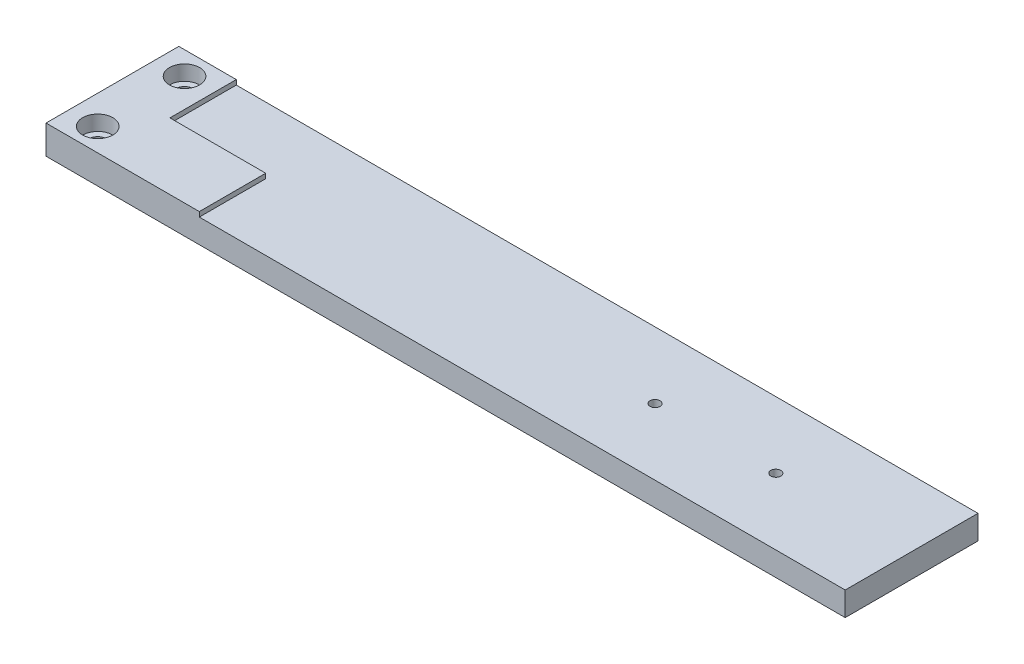
SolidWorks part; units mm, degrees
material "6061 Alloy"
ref_plane "Front" through (0, 0, 0) normal (0, 0, 1) x (1, 0, 0)
ref_plane "Top" through (0, 0, 0) normal (0, 1, 0) x (1, 0, 0)
ref_plane "Right" through (0, 0, 0) normal (1, 0, 0) x (0, 0, -1)
sketch "Sketch1" plane through (0, 0, 0) normal (0, 1, 0) x (1, 0, 0)
  line L1 (0, 0) -> (220.35, 0)
  line L2 (0, 0) -> (0, 44)
  line L3 (0, 44) -> (220.35, 44)
  line L4 (220.35, 0) -> (220.35, 44)
  dimension "D1" = 44
  dimension "D2" = 220.35
extrude "Boss-Extrude1" add sketch "Sketch1" along normal blind 7.9375
sketch "Sketch2" plane through (0, 7.9375, 0) normal (0, 1, 0) x (1, 0, 0)
  line L1 (0, 0) -> (6.35, 0)
  line L2 (0, 0) -> (0, 22)
  line L3 (0, 22) -> (6.35, 22)
  line L4 (6.35, 0) -> (6.35, 22)
  line L5 (0, 0) -> (220.35, 0) construction
  dimension "D1" = 6.35
  dimension "D2" = 22
extrude "Boss-Extrude2" add sketch "Sketch2" along normal blind 1.5875
hole_wizard "M4x0.7 Tapped Hole2" positions "Sketch5" profile "Sketch6" tap size "M4x0.7" standard "ANSI Metric" end condition through all
sketch "Sketch5" plane through (0, 7.9375, 0) normal (0, 1, 0) x (1, 0, 0)
  line L0 (220.35, 22) -> (135.35, 22) construction
  line L1 (220.35, 0) -> (220.35, 44) construction
  point P0 (135.35, 22)
  point P2 (175.35, 22)
  dimension "D1" = 85
  dimension "D2" = 40
sketch "Sketch6" plane through (135.35, 7.9375, -22) normal (1, 0, 0) x (0, 0, 1)
  line L0 (0, 0) -> (0, 7.9375)
  line L1 (0, 7.9375) -> (1.65, 7.9375)
  line L2 (1.65, 7.9375) -> (1.65, 0)
  line L5 (1.65, 0) -> (0, 0)
  line L11 (0, -6.35) -> (0, 107.95) construction
  dimension "Thru Tap Drill Dia." = 3.3
  dimension "Thru Tap Drill Depth" = 7.9375
cosmetic thread "Hole Thread1" parameters "D2"=4
cosmetic thread "Hole Thread2" parameters "D2"=4
sketch "Sketch7" plane through (0, 0, 0) normal (0, 1, 0) x (1, 0, 0)
  line L0 (0, -50) -> (0, 50) construction
  line L1 (0, 44) -> (-44.45, 44)
  line L2 (0, 44) -> (0, 0)
  line L3 (0, 0) -> (-44.45, 0)
  line L4 (-44.45, 44) -> (-44.45, 0)
  line L5 (220.35, 44) -> (0, 44) construction
  line L6 (-50, 0) -> (50, 0) construction
  dimension "D1" = 44.45
extrude "Boss-Extrude3" add sketch "Sketch7" along normal blind 9.525
hole_wizard "CBORE for M5 SHCS1" positions "Sketch12" profile "Sketch13" counterbore size "M5" standard "ANSI Metric" end condition through all
sketch "Sketch12" plane through (0, 9.525, 0) normal (0, 1, 0) x (1, 0, 0)
  line L1 (0, 44) -> (-44.45, 44) construction
  line L2 (-50, 0) -> (50, 0) construction
  line L3 (-44.45, 44) -> (-44.45, 0) construction
  point P0 (-34.925, 36.38)
  point P2 (-34.925, 7.62)
  dimension "D1" = 7.62
  dimension "D2" = 7.62
  dimension "D3" = 9.525
  dimension "D4" = 9.525
sketch "Sketch13" plane through (-34.925, 9.525, -36.38) normal (1, 0, 0) x (0, 0, 1)
  line L0 (0, 0) -> (0, 9.525)
  line L1 (0, 9.525) -> (2.9, 9.525)
  line L3 (2.9, 9.525) -> (2.9, 5)
  line L4 (2.9, 5) -> (5, 5)
  line L5 (5, 5) -> (5, 0)
  line L7 (5, 0) -> (0, 0)
  line L11 (0, -6.35) -> (0, 107.95) construction
  dimension "Thru Hole Dia." = 5.8
  dimension "Thru Hole Depth" = 9.525
  dimension "C'Bore Dia." = 10
  dimension "C'Bore Depth" = 5
sketch "Sketch14" plane through (0, 9.525, 0) normal (0, 1, 0) x (1, 0, 0)
  line L0 (0, -50) -> (0, 50) construction
  line L1 (0, 44) -> (-25.4, 44)
  line L2 (0, 44) -> (0, 22)
  line L3 (0, 22) -> (-25.4, 22)
  line L4 (-25.4, 44) -> (-25.4, 22)
  line L5 (0, 44) -> (-44.45, 44) construction
  line L9 (6.35, 22) -> (0, 22) construction
  dimension "D1" = 25.4
extrude "Cut-Extrude1" cut sketch "Sketch14" along direction (0, -1, 0) on the side against the normal up to surface (1.5875 mm away) up to face at (135.35, 7.9375, -20.35)
